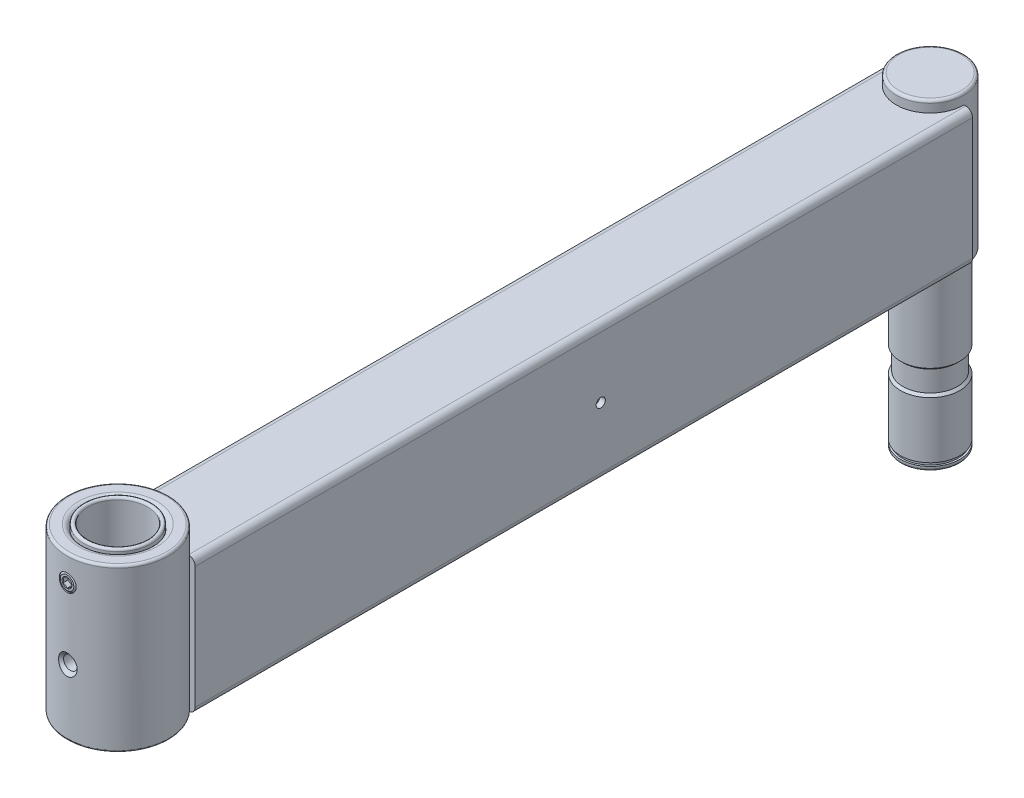
SolidWorks part; units mm, degrees
ref_plane "Front" through (0, 0, 0) normal (0, 0, 1) x (1, 0, 0)
ref_plane "Top" through (0, 0, 0) normal (0, 1, 0) x (1, 0, 0)
ref_plane "Right" through (0, 0, 0) normal (1, 0, 0) x (0, 0, -1)
sketch "Sketch1" plane through (0, 0, 0) normal (0, 0, 1) x (1, 0, 0)
  line L0 (0, -60.833) -> (0, 60.833) construction
  line L1 (0, -60.833) -> (-10.3403, -60.833)
  line L2 (-11.1023, -60.071) -> (-11.1023, -59.309)
  line L3 (-11.1023, -59.309) -> (-10.4292, -59.309)
  line L4 (-10.4292, -59.309) -> (-10.4292, -58.1152)
  line L5 (-10.4292, -58.1152) -> (-11.1023, -58.1152)
  line L6 (-11.1023, -58.1152) -> (-11.1023, -36.957)
  line L7 (-11.1023, -36.957) -> (-10.226, -36.0807)
  line L8 (-10.226, -36.0807) -> (-10.226, -28.3083)
  line L9 (-10.226, -28.3083) -> (-11.1023, -27.432)
  line L10 (-11.1023, -27.432) -> (-11.1023, 4.318)
  line L11 (-11.1023, 4.318) -> (-12.7, 4.318)
  line L12 (-12.7, 4.318) -> (-12.7, 59.817)
  line L13 (-11.684, 60.833) -> (0, 60.833)
  line L14 (0, -60.833) -> (0, 60.833)
  arc A0 (-11.1023, -60.071) -> (-10.3403, -60.833) centre (-10.3403, -60.071) ccw
  arc A1 (-11.684, 60.833) -> (-12.7, 59.817) centre (-11.684, 59.817) ccw
  dimension "D2" = 1.524
  dimension "D13" = 1.016
  dimension "D1" = 121.666
  dimension "D3" = 0.762
  dimension "D4" = 22.2047
  dimension "D5" = 20.8585
  dimension "D6" = 1.1938
  dimension "D7" = 21.1582
  dimension "D8" = 20.4521
  dimension "D9" = 45
  dimension "D10" = 7.7724
  dimension "D11" = 31.75
  dimension "D12" = 25.4
revolve "Revolve1" add sketch "Sketch1" angle 360 mid plane about L0
sketch "Sketch2" plane through (0, 0, 0) normal (0, 0, 1) x (1, 0, 0)
  line L0 (-15.875, 54.102) -> (-15.875, 8.382)
  line L1 (-13.335, 5.842) -> (13.335, 5.842)
  line L2 (15.875, 8.382) -> (15.875, 54.102)
  line L3 (13.335, 56.642) -> (-13.335, 56.642)
  line L4 (0, 0) -> (0, 5.842) construction
  line L5 (11.684, 60.833) -> (-11.684, 60.833) construction
  line L6 (-13.335, 54.5338) -> (13.335, 54.5338)
  line L7 (13.7668, 54.102) -> (13.7668, 8.382)
  line L8 (13.335, 7.9502) -> (-13.335, 7.9502)
  line L9 (-13.7668, 8.382) -> (-13.7668, 54.102)
  line L10 (0, 56.642) -> (0, 54.5338) construction
  line L11 (13.7668, 31.242) -> (15.875, 31.242) construction
  arc A0 (13.335, 5.842) -> (15.875, 8.382) centre (13.335, 8.382) ccw
  arc A1 (-15.875, 8.382) -> (-13.335, 5.842) centre (-13.335, 8.382) ccw
  arc A2 (15.875, 54.102) -> (13.335, 56.642) centre (13.335, 54.102) ccw
  arc A3 (-15.875, 54.102) -> (-13.335, 56.642) centre (-13.335, 54.102) cw
  arc A4 (13.335, 54.5338) -> (13.7668, 54.102) centre (13.335, 54.102) cw
  arc A5 (-13.7668, 54.102) -> (-13.335, 54.5338) centre (-13.335, 54.102) cw
  arc A6 (13.7668, 8.382) -> (13.335, 7.9502) centre (13.335, 8.382) cw
  arc A7 (-13.335, 7.9502) -> (-13.7668, 8.382) centre (-13.335, 8.382) cw
  point P21 (-15.875, 5.842)
  point P24 (15.875, 56.642)
  point P27 (-15.875, 56.642)
  dimension "D5" = 2.54
  dimension "D1" = 31.75
  dimension "D2" = 50.8
  dimension "D3" = 4.191
  dimension "D4" = 2.1082
extrude "Boss-Extrude1" add sketch "Sketch2" along normal blind 291.6428
sketch "Sketch3" plane through (0, 5.842, 0) normal (0, -1, 0) x (1, 0, 0)
  line L0 (0, 0) -> (0, 304.8) construction
  circle A0 centre (0, 304.8) radius 19.05
  dimension "D2" = 38.1
  dimension "D1" = 304.8
extrude "Cut-Extrude1" cut sketch "Sketch3" against normal through all
sketch "Sketch4" plane through (0, 5.842, 0) normal (0, -1, 0) x (1, 0, 0)
  line L0 (0, 0) -> (0, 20.32) construction
  line L2 (-13.7765, 291.6428) -> (13.7765, 291.6428) construction
  line L3 (0, 291.6428) -> (0, 278.13) construction
  circle A0 centre (0, 20.32) radius 3.175
  circle A1 centre (0, 278.13) radius 3.175
  dimension "D1" = 20.32
  dimension "D3" = 6.35
  dimension "D2" = 13.5128
extrude "Cut-Extrude2" cut sketch "Sketch4" against normal up to next
sketch "Sketch5" plane through (0, 0, 0) normal (1, 0, 0) x (0, 0, -1)
  line L0 (-291.6428, 5.8807) -> (-291.6428, 5.842) construction
  line L1 (-291.1956, 5.842) -> (-291.6428, 5.842) construction
  line L2 (-285.75, 5.842) -> (-285.75, 6.35) construction
  line L5 (-285.75, 6.35) -> (-285.75, 65.659)
  line L6 (-285.75, 36.0045) -> (-304.8, 36.0045) construction
  line L7 (-304.8, 5.842) -> (-304.8, 66.167) construction
  line L8 (-286.258, 5.842) -> (-291.465, 5.842)
  line L9 (-291.465, 5.842) -> (-292.1, 6.477)
  line L10 (-286.639, 66.548) -> (-290.068, 66.548)
  line L11 (-292.1, 6.477) -> (-292.1, 64.516)
  line L12 (-285.75, 5.842) -> (-291.1956, 5.842) construction
  line L13 (-291.1956, 5.842) -> (0, 5.842) construction
  line L14 (-291.1956, 5.842) -> (-285.75, 5.842) construction
  arc A0 (-286.258, 5.842) -> (-285.75, 6.35) centre (-286.258, 6.35) ccw
  arc A1 (-285.75, 65.659) -> (-286.639, 66.548) centre (-286.639, 65.659) ccw
  arc A2 (-290.068, 66.548) -> (-292.1, 64.516) centre (-290.068, 64.516) ccw
  dimension "D1" = 1.016
  dimension "D2" = 1.778
  dimension "D8" = 4.064
  dimension "D3" = 38.1
  dimension "D4" = 26.67
  dimension "D5" = 60.325
  dimension "D6" = 25.4
  dimension "D7" = 0.635
  dimension "D9" = 5.8928
revolve "Revolve2" add sketch "Sketch5" angle 360 mid plane about L7
sketch "Sketch6" plane through (0, 0, 0) normal (1, 0, 0) x (0, 0, -1)
  line L0 (-290.068, 66.548) -> (-319.532, 66.548) construction
  line L1 (-292.1, 36.3855) -> (-292.1, 66.548)
  line L2 (-292.1, 6.477) -> (-292.1, 64.516) construction
  line L3 (-293.6875, 66.548) -> (-293.6875, 36.3855)
  line L4 (-304.8, 66.548) -> (-304.8, 5.842) construction
  line L5 (-318.135, 5.842) -> (-291.465, 5.842) construction
  line L6 (-292.1, 24.0983) -> (-292.1, 6.6357)
  line L7 (-304.8, 5.842) -> (-292.8938, 5.842) construction
  line L8 (-293.6875, 24.0983) -> (-293.6875, 6.6358)
  arc A0 (-292.1, 66.548) -> (-293.6875, 66.548) centre (-292.8938, 66.548) ccw
  arc A1 (-293.6875, 36.3855) -> (-292.1, 36.3855) centre (-292.8938, 36.3855) ccw
  arc A2 (-293.6875, 6.6358) -> (-292.1, 6.6357) centre (-292.8938, 6.6358) ccw
  arc A3 (-292.1, 24.0983) -> (-293.6875, 24.0983) centre (-292.8938, 24.0983) ccw
  dimension "D1" = 1.5875
  dimension "D2" = 30.1625
  dimension "D3" = 17.4625
revolve "Revolve3" add sketch "Sketch6" angle 360 mid plane about L4
sketch "Sketch7" plane through (0, 0, 0) normal (1, 0, 0) x (0, 0, -1)
  line L0 (-304.8, 60.198) -> (-323.85, 60.198)
  line L1 (-304.8, 5.842) -> (-304.8, 66.167) construction
  line L2 (-304.8, 60.198) -> (-304.8, 57.023)
  line L3 (-304.8, 57.023) -> (-323.85, 57.023)
  line L4 (-323.85, 57.023) -> (-323.85, 60.198)
  line L5 (-286.639, 66.548) -> (-322.961, 66.548) construction
  dimension "D1" = 3.175
  dimension "D2" = 9.525
  dimension "D3" = 19.05
revolve "Cut-Revolve1" cut sketch "Sketch7" angle 360 mid plane about L3
sketch "Sketch8" plane through (0, 0, 0) normal (1, 0, 0) x (0, 0, -1)
  line L0 (-323.85, 59.563) -> (-323.4054, 60.198)
  line L1 (-323.85, 57.023) -> (-323.85, 60.198) construction
  line L2 (-304.8, 60.198) -> (-323.85, 60.198) construction
  line L3 (-323.4054, 60.198) -> (-318.9351, 60.198)
  line L4 (-318.9351, 60.198) -> (-317.5, 58.7629)
  line L5 (-317.5, 58.7629) -> (-317.5, 57.023)
  line L6 (-304.8, 57.023) -> (-323.85, 57.023) construction
  line L7 (-317.5, 57.023) -> (-321.945, 57.023)
  line L8 (-321.945, 57.023) -> (-321.945, 58.6105)
  line L9 (-321.945, 58.6105) -> (-323.6049, 58.6105)
  line L10 (-323.6049, 58.6105) -> (-323.85, 58.8556)
  line L11 (-323.85, 58.8556) -> (-323.85, 59.563)
  line L12 (-321.945, 57.023) -> (-323.85, 57.023) construction
  dimension "D1" = 6.35
  dimension "D2" = 35
  dimension "D3" = 5.08
  dimension "D4" = 3.6652
  dimension "D5" = 3.175
  dimension "D6" = 45
  dimension "D7" = 1.905
  dimension "D8" = 3.4798
revolve "Revolve5" add sketch "Sketch8" angle 360 mid plane about L12
sketch "Sketch9" plane through (0, 0, 323.85) normal (0, 0, 1) x (1, 0, 0)
  line L0 (0, 57.023) -> (0, 58.8561) construction
  line L1 (0, 58.8561) -> (-1.5875, 57.9395)
  line L2 (-1.5875, 57.9395) -> (-1.5875, 56.1065)
  line L3 (-1.5875, 56.1065) -> (0, 55.1899)
  line L4 (0, 55.1899) -> (1.5875, 56.1065)
  line L5 (1.5875, 56.1065) -> (1.5875, 57.9395)
  line L6 (1.5875, 57.9395) -> (0, 58.8561)
  circle A0 centre (0, 57.023) radius 1.5875 construction
  circle A1 centre (0, 57.023) radius 1.5875 construction
extrude "Cut-Extrude3" cut sketch "Sketch9" against normal up to surface (1.905 mm away) up to face at (-1.5875, 57.023, 321.945)
sketch "Sketch10" plane through (0, 0, 0) normal (1, 0, 0) x (0, 0, -1)
  line L0 (-323.85, 57.023) -> (-323.85, 30.4038) construction
  line L1 (-323.85, 30.4038) -> (-304.8, 30.4038)
  line L2 (-304.8, 30.4038) -> (-304.8, 32.9565)
  line L3 (-304.8, 32.9565) -> (-322.5927, 32.9565)
  line L4 (-322.5927, 32.9565) -> (-323.85, 34.2138)
  line L5 (-323.85, 34.2138) -> (-323.85, 30.4038)
  line L7 (-304.8, 66.548) -> (-304.8, 32.9565) construction
  line L8 (-315.9125, 66.548) -> (-293.6875, 66.548) construction
  dimension "D1" = 26.6192
  dimension "D2" = 2.5527
  dimension "D3" = 3.81
  dimension "D4" = 45
revolve "Cut-Revolve2" cut sketch "Sketch10" angle 360 mid plane about L1
sketch "Sketch11" plane through (15.875, 0, 0) normal (1, 0, 0) x (0, 0, -1)
  line L0 (0, 31.242) -> (-139.4714, 31.242) construction
  line L1 (0, 8.382) -> (0, 54.102) construction
  circle A0 centre (-139.4714, 31.242) radius 1.7272
  dimension "D2" = 3.4544
  dimension "D1" = 139.4714
extrude "Cut-Extrude4" cut sketch "Sketch11" against normal up to next (2.1082 mm away)
sketch "Sketch12" plane through (-15.875, 0, 0) normal (-1, 0, 0) x (0, 0, 1)
  line L0 (291.6428, 31.242) -> (152.1714, 31.242) construction
  line L1 (291.6428, 54.102) -> (291.6428, 8.382) construction
  line L2 (0, 31.242) -> (139.4714, 31.242) construction
  circle A0 centre (152.1714, 31.242) radius 1.7272
  circle A1 centre (139.4714, 31.242) radius 1.7272 construction
extrude "Cut-Extrude5" cut sketch "Sketch12" against normal up to next (2.1082 mm away)
